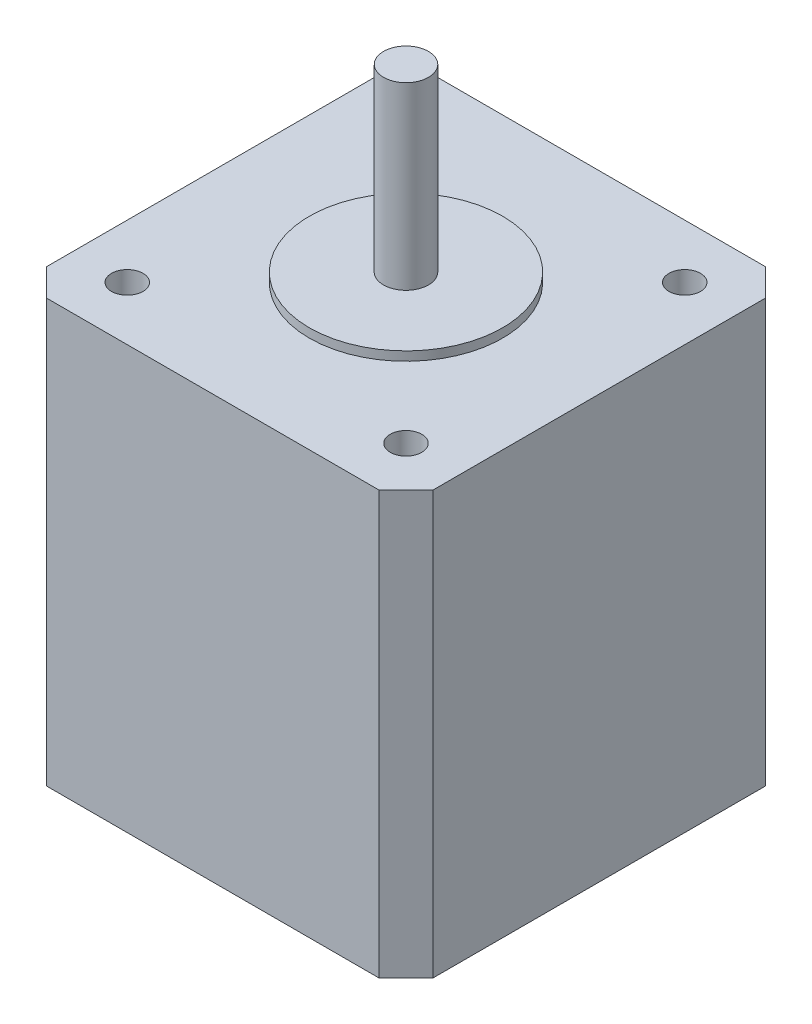
SolidWorks part; units mm, degrees
ref_plane "Front Plane" through (0, 0, 0) normal (0, 0, 1) x (1, 0, 0)
ref_plane "Top Plane" through (0, 0, 0) normal (0, 1, 0) x (1, 0, 0)
ref_plane "Right Plane" through (0, 0, 0) normal (1, 0, 0) x (0, 0, -1)
sketch "Sketch1" plane through (0, 0, 0) normal (0, 1, 0) x (1, 0, 0)
  line L1 (0, 0) -> (43, 0)
  line L2 (0, 0) -> (0, 43)
  line L3 (0, 43) -> (43, 43)
  line L4 (43, 0) -> (43, 43)
  dimension "D1" = 43
  dimension "D2" = 43
extrude "Boss-Extrude1" add sketch "Sketch1" along normal blind 47
sketch "Sketch2" plane through (0, 47, 0) normal (0, 1, 0) x (1, 0, 0)
  line L0 (0, 43) -> (43, 0) construction
  circle A0 centre (21.5, 21.5) radius 10.75
  dimension "D1" = 21.5
extrude "Boss-Extrude2" add sketch "Sketch2" along normal blind 1
sketch "Sketch3" plane through (0, 48, 0) normal (0, 1, 0) x (1, 0, 0)
  circle A0 centre (21.5, 21.5) radius 2.5
  circle A1 centre (21.5, 21.5) radius 10.75 construction
  dimension "D1" = 5
extrude "Boss-Extrude3" add sketch "Sketch3" along normal blind 20
chamfer "Chamfer1" distance 3 angle 45 4 edges at (0, 23.5, -43) (43, 23.5, -43) (43, 23.5, 0) (0, 23.5, 0)
sketch "Sketch4" plane through (0, 47, 0) normal (0, 1, 0) x (1, 0, 0)
  line L1 (6, 6) -> (37, 6) construction
  line L2 (6, 6) -> (6, 37) construction
  line L3 (6, 37) -> (37, 37) construction
  line L4 (37, 6) -> (37, 37) construction
  line L5 (0, 0) -> (41.5, 41.5) construction
  line L6 (43, 40) -> (40, 43) construction
  line L7 (1.5, 41.5) -> (41.5, 1.5) construction
  line L8 (3, 43) -> (0, 40) construction
  line L9 (40, 0) -> (43, 3) construction
  circle A2 centre (6, 37) radius 1.75
  circle A3 centre (6, 6) radius 1.75
  circle A4 centre (37, 6) radius 1.75
  circle A5 centre (37, 37) radius 1.75
  dimension "D1" = 31
  dimension "D3" = 3.5
  dimension "D4" = 3.5
  dimension "D5" = 3.5
  dimension "D6" = 3.5
  dimension "D2" = 31
extrude "Cut-Extrude2" cut sketch "Sketch4" against normal blind 10
